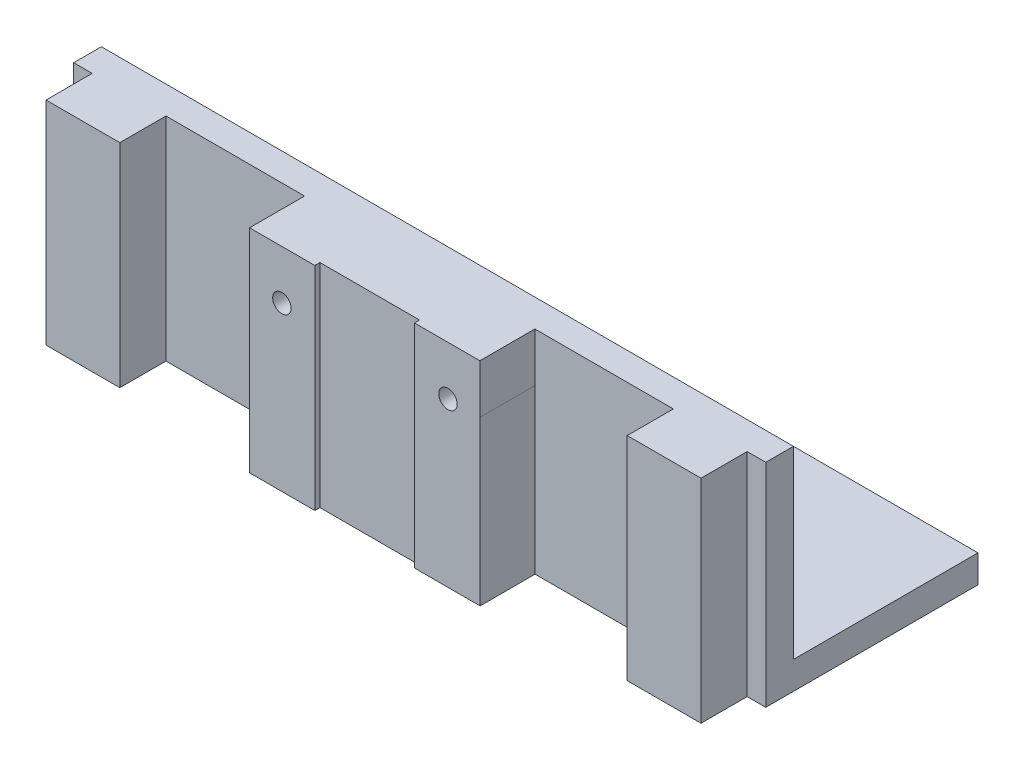
SolidWorks part; units mm, degrees
ref_plane "Front Plane" through (0, 0, 0) normal (0, 0, 1) x (1, 0, 0)
ref_plane "Top Plane" through (0, 0, 0) normal (0, 1, 0) x (1, 0, 0)
ref_plane "Right Plane" through (0, 0, 0) normal (1, 0, 0) x (0, 0, -1)
sketch "Sketch1" plane through (0, 0, 0) normal (0, 1, 0) x (1, 0, 0)
  line L1 (-25, -11.5) -> (25, -11.5)
  line L2 (-25, -11.5) -> (-25, 11.5)
  line L3 (-25, 11.5) -> (25, 11.5)
  line L4 (25, -11.5) -> (25, 11.5)
  line L5 (-25, -11.5) -> (25, 11.5) construction
  line L6 (-25, 11.5) -> (25, -11.5) construction
  point P0 (0, 0)
extrude "Boss-Extrude12" add sketch "Sketch1" along normal blind 3
sketch "Sketch17" plane through (0, 3, 0) normal (0, 1, 0) x (1, 0, 0)
  line L0 (25, -11.5) -> (25, 11.5) construction
  line L1 (-25, -11.5) -> (25, -11.5)
  line L2 (-25, -11.5) -> (-25, -8.5)
  line L3 (-25, -8.5) -> (25, -8.5)
  line L4 (25, -11.5) -> (25, -8.5)
extrude "Boss-Extrude13" add sketch "Sketch17" along normal blind 20
sketch "Sketch18" plane through (25, 0, 0) normal (1, 0, 0) x (0, 0, -1)
  line L0 (-11.5, 23) -> (-8.5, 23)
  line L1 (-8.5, 23) -> (-8.5, 3)
  line L2 (-8.5, 3) -> (11.5, 3)
  line L3 (11.5, 3) -> (11.5, 0)
  line L4 (11.5, 0) -> (-11.5, 0)
  line L5 (-11.5, 0) -> (-11.5, 23)
extrude "Boss-Extrude15" add sketch "Sketch18" along normal blind 25
sketch "Sketch19" plane through (0, 0, 0) normal (0, -1, 0) x (1, 0, 0)
  circle A0 centre (-7.5, -1.0693) radius 3
  circle A1 centre (12.5, -1.0693) radius 3
  circle A2 centre (32.5, -1.0693) radius 3
extrude "Cut-Extrude1" cut sketch "Sketch19" against normal blind 10
sketch "Sketch20" plane through (0, 0, 0) normal (0, -1, 0) x (1, 0, 0)
  circle A3 centre (-7.5, -1.0693) radius 3
  circle A4 centre (12.5, -1.0693) radius 3
  circle A5 centre (32.5, -1.0693) radius 3
  circle A6 centre (-7.5, -1.0693) radius 4
  circle A7 centre (12.5, -1.0693) radius 4
  circle A8 centre (32.5, -1.0693) radius 4
extrude "Boss-Extrude16" add sketch "Sketch20" along normal blind 2.5
sketch "Sketch21" plane through (0, 0, 11.5) normal (0, 0, 1) x (1, 0, 0)
  line L1 (-25, 23) -> (50, 23) construction
  line L4 (0.0228, 17.6839) -> (0, 0)
  line L5 (0, 0) -> (25, 0)
  line L6 (0.0228, 17.6839) -> (0.0228, 23)
  line L7 (0.0228, 23) -> (24.9772, 23)
  line L8 (24.9772, 17.6839) -> (24.9772, 23)
  line L9 (24.9772, 17.6839) -> (25, 0)
  arc A0 (1.7156, 21.4339) -> (1.7156, 13.9339) centre (5.0228, 17.6839) ccw construction
extrude "Boss-Extrude17" add sketch "Sketch21" along normal blind 5.96
sketch "Sketch22" plane through (0, 23, 0) normal (0, 1, 0) x (1, 0, 0)
  line L0 (15.8929, -16.909) -> (17.8908, -16.909)
  line L1 (17.8908, -16.909) -> (17.8908, -17.46)
  line L2 (24.9772, -17.46) -> (0.0228, -17.46) construction
  line L3 (15.8929, -16.909) -> (9.0929, -16.909)
  line L4 (9.0929, -16.909) -> (7.0929, -16.909)
  line L5 (7.0929, -16.909) -> (7.0929, -17.46)
  line L6 (7.0929, -17.46) -> (17.8908, -17.46)
extrude "Cut-Extrude2" cut sketch "Sketch22" against normal through all
sketch "Sketch23" plane through (0, 0, 17.46) normal (0, 0, 1) x (1, 0, 0)
  circle A0 centre (3.5228, 17.6839) radius 1
  circle A1 centre (21.5228, 17.6839) radius 1
extrude "Cut-Extrude3" cut sketch "Sketch23" against normal through all
sketch "Sketch24" plane through (0, 0, 11.5) normal (0, 0, 1) x (1, 0, 0)
  line L1 (-25, 23) -> (0.0228, 23) construction
  line L2 (-23, 23) -> (-23, 0)
  line L3 (-25, 0) -> (0, 0) construction
  line L4 (-23, 0) -> (-15, 0)
  line L5 (-15, 0) -> (-15, 23)
  line L6 (-15, 23) -> (-23, 23)
  line L13 (39.9837, 23) -> (47.9837, 23)
  line L14 (39.9837, 0) -> (39.9837, 23)
  line L15 (47.9837, 0) -> (39.9837, 0)
  line L16 (47.9837, 23) -> (47.9837, 0)
extrude "Boss-Extrude20" add sketch "Sketch24" along normal blind 5
